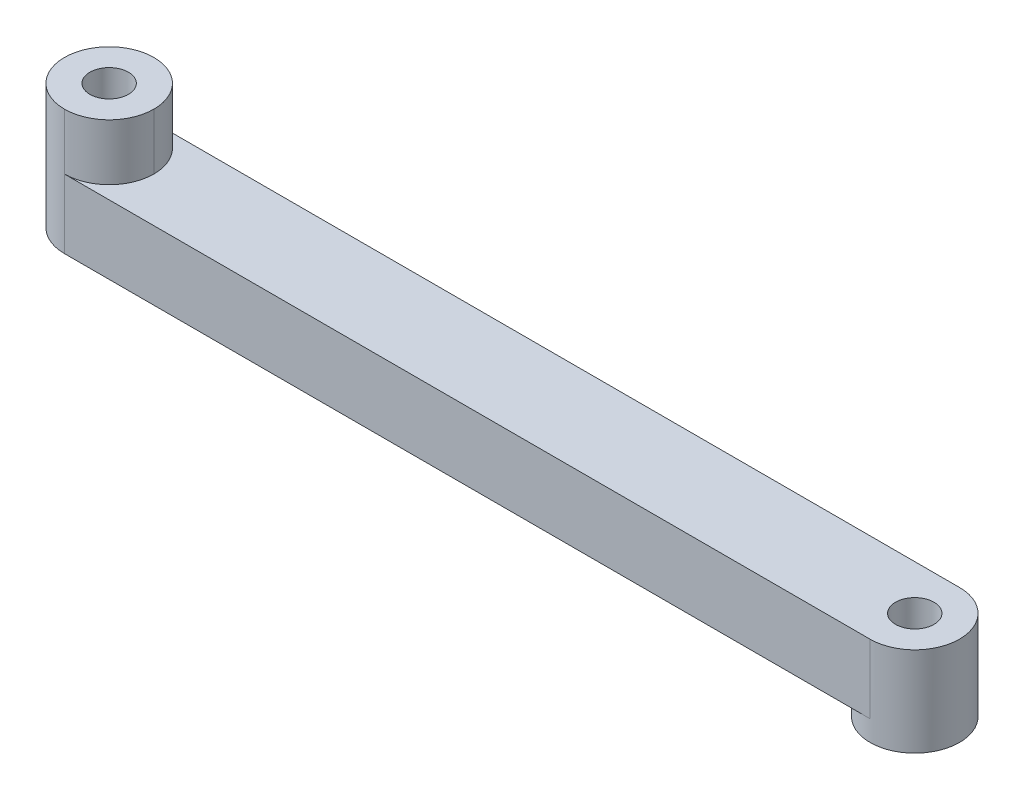
SolidWorks part; units mm, degrees
ref_plane "정면" through (0, 0, 0) normal (0, 0, 1) x (1, 0, 0)
ref_plane "윗면" through (0, 0, 0) normal (0, 1, 0) x (1, 0, 0)
ref_plane "우측면" through (0, 0, 0) normal (1, 0, 0) x (0, 0, -1)
sketch "스케치1" plane through (0, 0, 0) normal (0, 0, 1) x (1, 0, 0)
  line L1 (-50, -3.85) -> (50, -3.85)
  line L2 (-50, -3.85) -> (-50, 3.85)
  line L3 (-50, 3.85) -> (50, 3.85)
  line L4 (50, -3.85) -> (50, 3.85)
  line L5 (-50, -3.85) -> (50, 3.85) construction
  line L6 (-50, 3.85) -> (50, -3.85) construction
  point P0 (0, 0)
  dimension "D1" = 100
  dimension "D2" = 7.7
extrude "보스-돌출1" add sketch "스케치1" along normal blind 10
sketch "스케치4" plane through (0, 3.85, 0) normal (0, 1, 0) x (1, 0, 0)
  line L0 (50, 0) -> (-50, 0) construction
  line L1 (-40, 0) -> (-50, 0)
  line L2 (-40, 0) -> (-40, -10)
  line L3 (-40, -10) -> (-50, -10)
  line L4 (-50, 0) -> (-50, -10)
  dimension "D1" = 10
extrude "보스-돌출2" add sketch "스케치4" along normal blind 6.28
fillet "필렛1" radius 5 6 edges at (50, 0, 10) (50, 0, 0) (-50, 3.14, 0) (-50, 3.14, 10) (-40, 6.99, 10) (-40, 6.99, 0)
sketch "스케치2" plane through (0, 10.13, 0) normal (0, 1, 0) x (1, 0, 0)
  circle A0 centre (-45, -5) radius 2.15
  circle A1 centre (45, -5) radius 2.15
  dimension "D1" = 4.3
  dimension "D2" = 4.3
extrude "컷-돌출1" cut sketch "스케치2" against normal through all
sketch "스케치5" plane through (0, -3.85, 0) normal (0, -1, 0) x (1, 0, 0)
  circle A0 centre (45, 5) radius 5
  circle A1 centre (45, 5) radius 2.15
extrude "보스-돌출3" add sketch "스케치5" along normal blind 2.3
